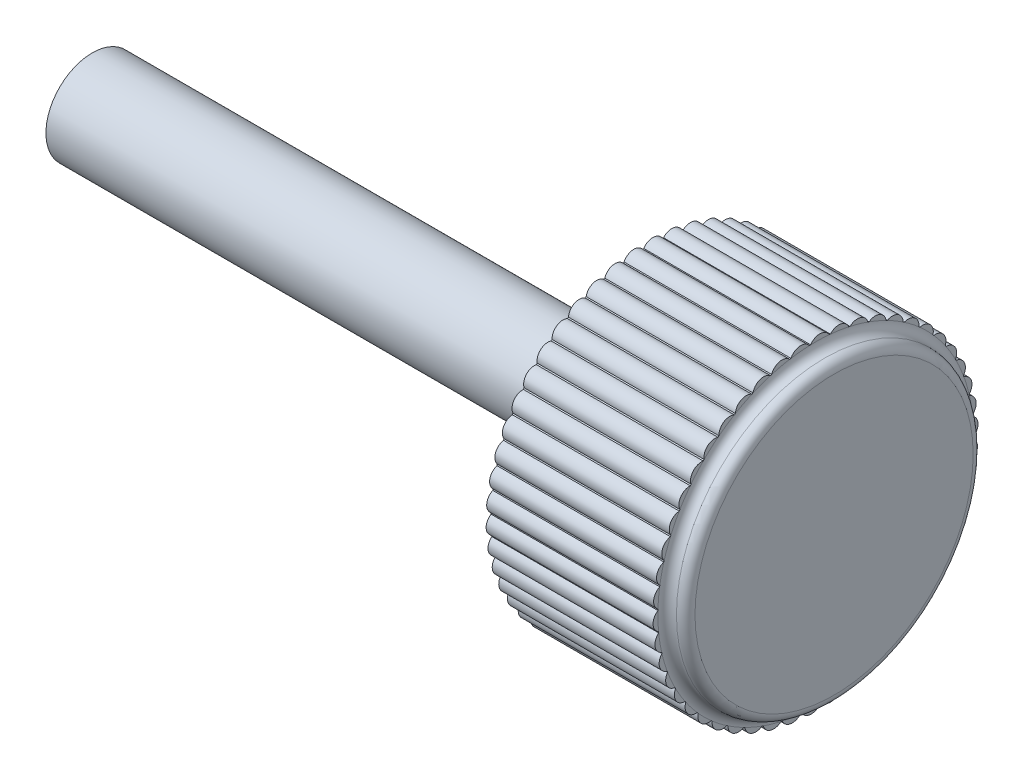
SolidWorks part; units mm, degrees
ref_plane "Front Plane" through (0, 0, 0) normal (0, 0, 1) x (1, 0, 0)
ref_plane "Top Plane" through (0, 0, 0) normal (0, 1, 0) x (1, 0, 0)
ref_plane "Right Plane" through (0, 0, 0) normal (1, 0, 0) x (0, 0, -1)
sketch "Sketch1" plane through (0, 0, 0) normal (1, 0, 0) x (0, 0, -1)
  circle A0 centre (0, 0) radius 0.635
  dimension "D1" = 1.27
extrude "Extrude1" add sketch "Sketch1" along normal blind 7.62
sketch "Sketch2" plane through (7.62, 0, 0) normal (1, 0, 0) x (0, 0, -1)
  circle A0 centre (0, 0) radius 2.032
  dimension "D1" = 4.064
extrude "Extrude2" add sketch "Sketch2" along normal blind 2.54
ref_plane "Plane1" through (9.906, 0, 0) normal (1, 0, 0) x (0, 0, -1)
sketch "Sketch3" plane through (9.906, 0, 0) normal (1, 0, 0) x (0, 0, -1)
  arc A0 (-1.8577, 1.1001) -> (-1.8663, 1.0854) centre (0, 0) ccw
  arc A1 (-2.1584, 0.0521) -> (-2.1495, -0.2019) centre (-2.0765, -0.0723) ccw
  arc A2 (-2.1348, 0.3222) -> (-2.1579, 0.0691) centre (-2.0692, 0.1886) ccw
  arc A3 (-2.0776, 0.5872) -> (-2.1322, 0.339) centre (-2.0293, 0.4464) ccw
  arc A4 (-1.9876, 0.8429) -> (-2.0729, 0.6035) centre (-1.9573, 0.6972) ccw
  arc A5 (-1.8663, 1.0854) -> (-1.9809, 0.8586) centre (-1.8545, 0.9371) ccw
  arc A6 (-1.7156, 1.3108) -> (-1.8577, 1.1001) centre (-1.7224, 1.1621) ccw
  arc A7 (-1.5378, 1.5155) -> (-1.7052, 1.3242) centre (-1.5632, 1.3688) ccw
  arc A8 (-1.3357, 1.6962) -> (-1.5258, 1.5275) centre (-1.3793, 1.5539) ccw
  arc A9 (-1.1126, 1.8503) -> (-1.3223, 1.7067) centre (-1.1737, 1.7146) ccw
  arc A10 (-0.8719, 1.9751) -> (-1.098, 1.859) centre (-0.9495, 1.8481) ccw
  arc A11 (-0.6175, 2.0688) -> (-0.8563, 1.9819) centre (-0.7104, 1.9526) ccw
  arc A12 (-0.3533, 2.1299) -> (-0.6012, 2.0736) centre (-0.4601, 2.0262) ccw
  arc A13 (-0.0836, 2.1574) -> (-0.3365, 2.1326) centre (-0.2025, 2.0679) ccw
  arc A14 (0.1875, 2.1508) -> (-0.0666, 2.158) centre (0.0583, 2.077) ccw
  arc A15 (0.4556, 2.1104) -> (0.2044, 2.1493) centre (0.3181, 2.0533) ccw
  arc A16 (0.7165, 2.0366) -> (0.4722, 2.1067) centre (0.573, 1.9972) ccw
  arc A17 (0.9661, 1.9308) -> (0.7325, 2.0309) centre (0.8188, 1.9097) ccw
  arc A18 (1.2005, 1.7945) -> (0.9813, 1.9231) centre (1.0517, 1.792) ccw
  arc A19 (1.4159, 1.6299) -> (1.2146, 1.785) centre (1.268, 1.6461) ccw
  arc A20 (1.609, 1.4396) -> (1.4287, 1.6187) centre (1.4643, 1.4742) ccw
  arc A21 (1.7768, 1.2265) -> (1.6203, 1.4268) centre (1.6375, 1.279) ccw
  arc A22 (1.9165, 0.9942) -> (1.7864, 1.2125) centre (1.7849, 1.0637) ccw
  arc A23 (2.026, 0.7462) -> (1.9242, 0.9791) centre (1.9041, 0.8316) ccw
  arc A24 (2.1035, 0.4863) -> (2.0318, 0.7302) centre (1.9933, 0.5864) ccw
  arc A25 (2.1479, 0.2189) -> (2.1073, 0.4698) centre (2.0511, 0.3319) ccw
  arc A26 (2.1584, -0.0521) -> (2.1495, 0.2019) centre (2.0765, 0.0723) ccw
  arc A27 (2.1348, -0.3222) -> (2.1579, -0.0691) centre (2.0692, -0.1886) ccw
  arc A28 (2.0776, -0.5872) -> (2.1322, -0.339) centre (2.0293, -0.4464) ccw
  arc A29 (1.9876, -0.8429) -> (2.0729, -0.6035) centre (1.9573, -0.6972) ccw
  arc A30 (1.8663, -1.0854) -> (1.9809, -0.8586) centre (1.8545, -0.9371) ccw
  arc A31 (1.7156, -1.3108) -> (1.8577, -1.1001) centre (1.7224, -1.1621) ccw
  arc A32 (1.5378, -1.5155) -> (1.7052, -1.3242) centre (1.5632, -1.3688) ccw
  arc A33 (1.3357, -1.6962) -> (1.5258, -1.5275) centre (1.3793, -1.5539) ccw
  arc A34 (1.1126, -1.8503) -> (1.3223, -1.7067) centre (1.1737, -1.7146) ccw
  arc A35 (0.8719, -1.9751) -> (1.098, -1.859) centre (0.9495, -1.8481) ccw
  arc A36 (0.6175, -2.0688) -> (0.8563, -1.9819) centre (0.7104, -1.9526) ccw
  arc A37 (0.3533, -2.1299) -> (0.6012, -2.0736) centre (0.4601, -2.0262) ccw
  arc A38 (0.0836, -2.1574) -> (0.3365, -2.1326) centre (0.2025, -2.0679) ccw
  arc A39 (-0.1875, -2.1508) -> (0.0666, -2.158) centre (-0.0583, -2.077) ccw
  arc A40 (-0.4556, -2.1104) -> (-0.2044, -2.1493) centre (-0.3181, -2.0533) ccw
  arc A41 (-0.7165, -2.0366) -> (-0.4722, -2.1067) centre (-0.573, -1.9972) ccw
  arc A42 (-0.9661, -1.9308) -> (-0.7325, -2.0309) centre (-0.8188, -1.9097) ccw
  arc A43 (-1.2005, -1.7945) -> (-0.9813, -1.9231) centre (-1.0517, -1.792) ccw
  arc A44 (-1.4159, -1.6299) -> (-1.2146, -1.785) centre (-1.268, -1.6461) ccw
  arc A45 (-1.609, -1.4396) -> (-1.4287, -1.6187) centre (-1.4643, -1.4742) ccw
  arc A46 (-1.7768, -1.2265) -> (-1.6203, -1.4268) centre (-1.6375, -1.279) ccw
  arc A47 (-1.9165, -0.9942) -> (-1.7864, -1.2125) centre (-1.7849, -1.0637) ccw
  arc A48 (-2.026, -0.7462) -> (-1.9242, -0.9791) centre (-1.9041, -0.8316) ccw
  arc A49 (-2.1035, -0.4863) -> (-2.0318, -0.7302) centre (-1.9933, -0.5864) ccw
  arc A50 (-2.1479, -0.2189) -> (-2.1073, -0.4698) centre (-2.0511, -0.3319) ccw
  arc A51 (-1.7052, 1.3242) -> (-1.7156, 1.3108) centre (0, 0) ccw
  arc A52 (-1.5258, 1.5275) -> (-1.5378, 1.5155) centre (0, 0) ccw
  arc A53 (-1.3223, 1.7067) -> (-1.3357, 1.6962) centre (0, 0) ccw
  arc A54 (-1.098, 1.859) -> (-1.1126, 1.8503) centre (0, 0) ccw
  arc A55 (-0.8563, 1.9819) -> (-0.8719, 1.9751) centre (0, 0) ccw
  arc A56 (-0.6012, 2.0736) -> (-0.6175, 2.0688) centre (0, 0) ccw
  arc A57 (-0.3365, 2.1326) -> (-0.3533, 2.1299) centre (0, 0) ccw
  arc A58 (-0.0666, 2.158) -> (-0.0836, 2.1574) centre (0, 0) ccw
  arc A59 (0.2044, 2.1493) -> (0.1875, 2.1508) centre (0, 0) ccw
  arc A60 (0.4722, 2.1067) -> (0.4556, 2.1104) centre (0, 0) ccw
  arc A61 (0.7325, 2.0309) -> (0.7165, 2.0366) centre (0, 0) ccw
  arc A62 (0.9813, 1.9231) -> (0.9661, 1.9308) centre (0, 0) ccw
  arc A63 (1.2146, 1.785) -> (1.2005, 1.7945) centre (0, 0) ccw
  arc A64 (1.4287, 1.6187) -> (1.4159, 1.6299) centre (0, 0) ccw
  arc A65 (1.6203, 1.4268) -> (1.609, 1.4396) centre (0, 0) ccw
  arc A66 (1.7864, 1.2125) -> (1.7768, 1.2265) centre (0, 0) ccw
  arc A67 (1.9242, 0.9791) -> (1.9165, 0.9942) centre (0, 0) ccw
  arc A68 (2.0318, 0.7302) -> (2.026, 0.7462) centre (0, 0) ccw
  arc A69 (2.1073, 0.4698) -> (2.1035, 0.4863) centre (0, 0) ccw
  arc A70 (2.1495, 0.2019) -> (2.1479, 0.2189) centre (0, 0) ccw
  arc A71 (2.1579, -0.0691) -> (2.1584, -0.0521) centre (0, 0) ccw
  arc A72 (2.0729, -0.6035) -> (2.0776, -0.5872) centre (0, 0) ccw
  arc A73 (2.1322, -0.339) -> (2.1348, -0.3222) centre (0, 0) ccw
  arc A74 (1.9809, -0.8586) -> (1.9876, -0.8429) centre (0, 0) ccw
  arc A75 (1.8577, -1.1001) -> (1.8663, -1.0854) centre (0, 0) ccw
  arc A76 (1.7052, -1.3242) -> (1.7156, -1.3108) centre (0, 0) ccw
  arc A77 (1.5258, -1.5275) -> (1.5378, -1.5155) centre (0, 0) ccw
  arc A78 (1.3223, -1.7067) -> (1.3357, -1.6962) centre (0, 0) ccw
  arc A79 (1.098, -1.859) -> (1.1126, -1.8503) centre (0, 0) ccw
  arc A80 (0.8563, -1.9819) -> (0.8719, -1.9751) centre (0, 0) ccw
  arc A81 (0.6012, -2.0736) -> (0.6175, -2.0688) centre (0, 0) ccw
  arc A82 (0.3365, -2.1326) -> (0.3533, -2.1299) centre (0, 0) ccw
  arc A83 (0.0666, -2.158) -> (0.0836, -2.1574) centre (0, 0) ccw
  arc A84 (-0.2044, -2.1493) -> (-0.1875, -2.1508) centre (0, 0) ccw
  arc A85 (-0.4722, -2.1067) -> (-0.4556, -2.1104) centre (0, 0) ccw
  arc A86 (-0.7325, -2.0309) -> (-0.7165, -2.0366) centre (0, 0) ccw
  arc A87 (-0.9813, -1.9231) -> (-0.9661, -1.9308) centre (0, 0) ccw
  arc A88 (-1.2146, -1.785) -> (-1.2005, -1.7945) centre (0, 0) ccw
  arc A89 (-1.4287, -1.6187) -> (-1.4159, -1.6299) centre (0, 0) ccw
  arc A90 (-1.6203, -1.4268) -> (-1.609, -1.4396) centre (0, 0) ccw
  arc A91 (-1.7864, -1.2125) -> (-1.7768, -1.2265) centre (0, 0) ccw
  arc A92 (-1.9242, -0.9791) -> (-1.9165, -0.9942) centre (0, 0) ccw
  arc A93 (-2.0318, -0.7302) -> (-2.026, -0.7462) centre (0, 0) ccw
  arc A94 (-2.1073, -0.4698) -> (-2.1035, -0.4863) centre (0, 0) ccw
  arc A95 (-2.1495, -0.2019) -> (-2.1479, -0.2189) centre (0, 0) ccw
  arc A96 (-2.1579, 0.0691) -> (-2.1584, 0.0521) centre (0, 0) ccw
  arc A97 (-2.1322, 0.339) -> (-2.1348, 0.3222) centre (0, 0) ccw
  arc A98 (-2.0729, 0.6035) -> (-2.0776, 0.5872) centre (0, 0) ccw
  arc A99 (-1.9809, 0.8586) -> (-1.9876, 0.8429) centre (0, 0) ccw
  dimension "D2" = 4.318
  dimension "D1" = 0.254
extrude "Extrude6" add sketch "Sketch3" against normal blind 2.286
fillet "Fillet2" radius 0.127 2 edges at (10.16, 0, -2.032) (9.906, 0, -2.032)
